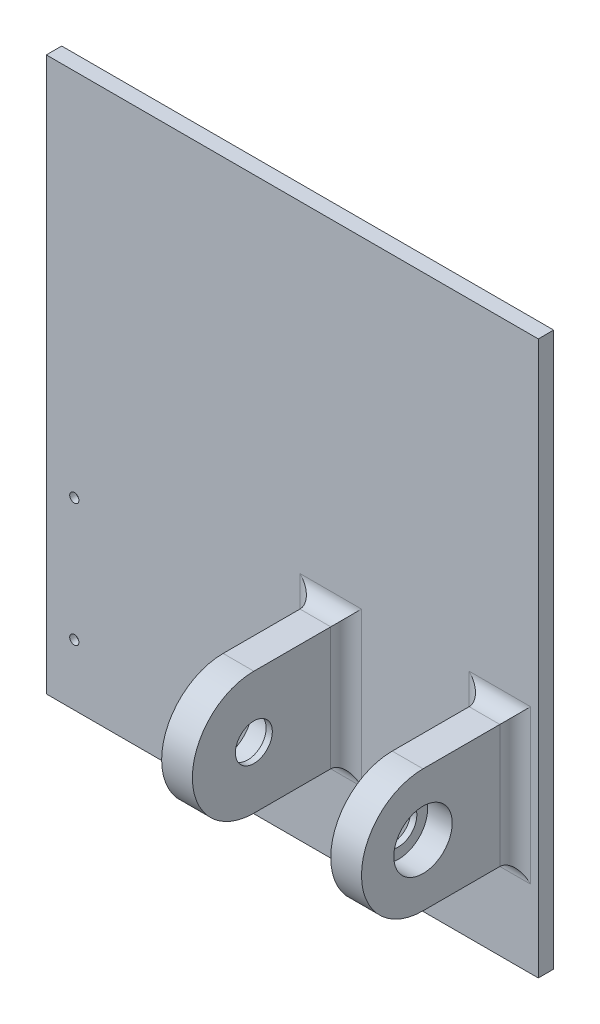
SolidWorks part; units mm, degrees
ref_plane "正面" through (0, 0, 0) normal (0, 0, 1) x (1, 0, 0)
ref_plane "平面" through (0, 0, 0) normal (0, 1, 0) x (1, 0, 0)
ref_plane "右側面" through (0, 0, 0) normal (1, 0, 0) x (0, 0, -1)
sketch "ｽｹｯﾁ2" plane through (0, 0, 0) normal (0, 0, 1) x (1, 0, 0)
  line L0 (-120, 99.8362) -> (-120, -80.1638)
  line L5 (-120, -80.1638) -> (40, -80.1638)
  line L6 (40, -80.1638) -> (40, 99.8362)
  line L7 (40, 99.8362) -> (-120, 99.8362)
  point P0 (0, 0)
  dimension "D1" = 180
  dimension "D2" = 120
  dimension "D3" = 40
extrude "ﾎﾞｽ - 押し出し1" add sketch "ｽｹｯﾁ2" along normal blind 5
sketch "ｽｹｯﾁ3" plane through (0, 0, 0) normal (0, 0, 1) x (1, 0, 0)
  line L0 (-32.5, -10) -> (-32.5, -50)
  line L1 (-32.5, -50) -> (-22.5, -50)
  line L2 (-22.5, -50) -> (-22.5, -10)
  line L3 (-22.5, -10) -> (-32.5, -10)
  dimension "D1" = 10
  dimension "D2" = 40
  dimension "D3" = 50
  dimension "D4" = 22.5
extrude "ﾎﾞｽ - 押し出し2" add sketch "ｽｹｯﾁ3" along normal blind 35
ref_plane "平面1" through (-32.5, 0, 0) normal (-1, 0, 0) x (0, 0, 1)
sketch "ｽｹｯﾁ4" plane through (-32.5, 0, 0) normal (-1, 0, 0) x (0, 0, 1)
  line L0 (35, -10) -> (35, -50) construction
  circle A0 centre (35, -30) radius 20
extrude "ﾎﾞｽ - 押し出し3" add sketch "ｽｹｯﾁ4" against normal blind 10
sketch "ｽｹｯﾁ5" plane through (-32.5, 0, 0) normal (-1, 0, 0) x (0, 0, 1)
  circle A0 centre (35, -30) radius 9.5
  dimension "D1" = 19
extrude "ｶｯﾄ - 押し出し1" cut sketch "ｽｹｯﾁ5" against normal blind 8
sketch "ｽｹｯﾁ13" plane through (-22.5, 0, 0) normal (1, 0, 0) x (0, 0, -1)
  circle A0 centre (-35, -30) radius 6
  dimension "D1" = 12
extrude "ｶｯﾄ - 押し出し2" cut sketch "ｽｹｯﾁ13" against normal through all
fillet "ﾌｨﾚｯﾄ1" radius 5 4 edges at (-27.5, -50, 5) (-32.5, -30, 5) (-27.5, -10, 5) (-22.5, -30, 5)
mirror "ﾐﾗｰ2" about plane through (0, 0, 0) normal (1, 0, 0) of "ﾌｨﾚｯﾄ1", "ｶｯﾄ - 押し出し2", "ｶｯﾄ - 押し出し1", "ﾎﾞｽ - 押し出し3", "ﾎﾞｽ - 押し出し2"
ref_plane "平面2" through (-22.5, 0, 0) normal (1, 0, 0) x (0, 0, -1)
sketch "ｽｹｯﾁ14" plane through (0, 0, 0) normal (0, 0, 1) x (1, 0, 0)
  circle A0 centre (-110.9, -20.35) radius 1.5
  circle A1 centre (-110.9, -60.35) radius 1.5
  dimension "D1" = 3
  dimension "D2" = 3
  dimension "D3" = 110.9
  dimension "D5" = 110.9
  dimension "D4" = 40
  dimension "D6" = 20.35
extrude "ｶｯﾄ - 押し出し3" cut sketch "ｽｹｯﾁ14" along normal blind 10
sketch "ｽｹｯﾁ15" plane through (0, 0, 0) normal (0, 0, 1) x (1, 0, 0)
  line L0 (-110.9, -20.35) -> (-110.9, -60.35) construction
  line L2 (-113.75, -21.9954) -> (-110.9, -23.6409)
  line L3 (-110.9, -23.6409) -> (-108.05, -21.9954)
  line L4 (-108.05, -21.9954) -> (-108.05, -18.7046)
  line L5 (-108.05, -18.7046) -> (-110.9, -17.0591)
  line L6 (-110.9, -17.0591) -> (-113.75, -18.7046)
  line L7 (-113.75, -18.7046) -> (-113.75, -21.9954)
  line L8 (-113.75, -61.9954) -> (-110.9, -63.6409)
  line L9 (-110.9, -63.6409) -> (-108.05, -61.9954)
  line L10 (-108.05, -61.9954) -> (-108.05, -58.7046)
  line L11 (-108.05, -58.7046) -> (-110.9, -57.0591)
  line L12 (-110.9, -57.0591) -> (-113.75, -58.7046)
  line L13 (-113.75, -58.7046) -> (-113.75, -61.9954)
  circle A0 centre (-110.9, -20.35) radius 3.381
  circle A1 centre (-110.9, -60.35) radius 2.85
  circle A2 centre (-110.9, -20.35) radius 2.85 construction
  circle A3 centre (-110.9, -60.35) radius 2.85 construction
  dimension "D1" = 5.7
  dimension "D2" = 5.7
  dimension "D3" = 5.7
extrude "ｶｯﾄ - 押し出し4" cut sketch "ｽｹｯﾁ15" along normal blind 3 contours A1 | L2 L3 L4 L5 L6 L7 | L8 L9 L10 L11 L12 L13
sketch "ｽｹｯﾁ16" plane through (0, 0, 5) normal (0, 0, 1) x (1, 0, 0)
  line L0 (-120, -80.1638) -> (-120, -50.1638)
  line L1 (-120, 99.8362) -> (-120, -80.1638) construction
  line L2 (-120, -50.1638) -> (40, -50.1638)
  line L3 (40, -80.1638) -> (40, 99.8362) construction
  line L4 (40, -50.1638) -> (40, -80.1638)
  line L5 (40, -80.1638) -> (-120, -80.1638)
  dimension "D1" = 30
equation "\"D5@ｽｹｯﾁ14\"=\"D3@ｽｹｯﾁ14\""
